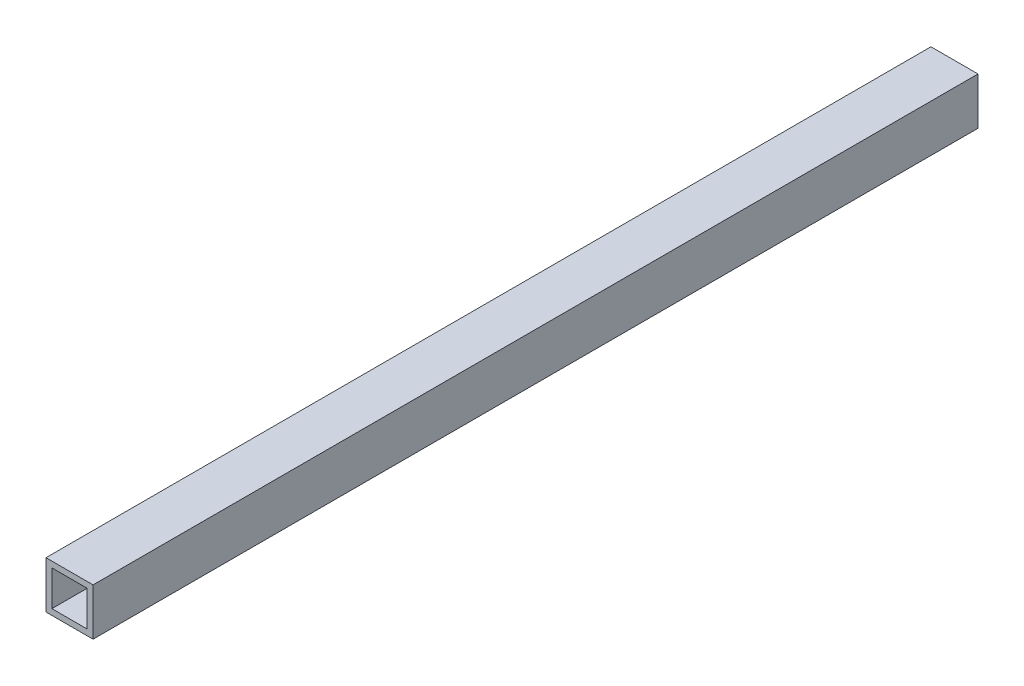
SolidWorks part; units mm, degrees
material "6061 Alloy"
ref_plane "Front Plane" through (0, 0, 0) normal (0, 0, 1) x (1, 0, 0)
ref_plane "Top Plane" through (0, 0, 0) normal (0, 1, 0) x (1, 0, 0)
ref_plane "Right Plane" through (0, 0, 0) normal (1, 0, 0) x (0, 0, -1)
sketch "Sketch1" plane through (0, 0, 0) normal (0, 0, 1) x (1, 0, 0)
  line L0 (12.7, 0) -> (9.525, 0) construction
  line L1 (-12.7, 0) -> (12.7, 0) construction
  line L2 (0, 12.7) -> (0, -12.7)
  point P7 (0, 0)
sketch "Sketch2" plane through (0, 0, 0) normal (1, 0, 0) x (0, 0, -1)
  line L0 (238.76, 0) -> (-238.76, 0)
  point P4 (0, 0)
  dimension "Length" = 477.52
sketch "Sketch3" plane through (0, 0, 0) normal (0, 0, 1) x (1, 0, 0)
  line L0 (-12.7, 0) -> (12.7, 0) construction
  line L5 (12.7, -12.7) -> (-12.7, -12.7)
  line L6 (12.7, -12.7) -> (12.7, 12.7)
  line L11 (12.7, 12.7) -> (-12.7, 12.7)
  line L12 (-12.7, -12.7) -> (-12.7, 12.7)
  line L14 (12.7, -12.7) -> (-12.7, 12.7) construction
  line L15 (12.7, 12.7) -> (-12.7, -12.7) construction
  line L16 (9.525, -9.525) -> (-9.525, -9.525)
  line L17 (9.525, -9.525) -> (9.525, 9.525)
  line L18 (9.525, 9.525) -> (-9.525, 9.525)
  line L19 (-9.525, -9.525) -> (-9.525, 9.525)
  line L20 (9.525, -9.525) -> (-9.525, 9.525) construction
  line L21 (9.525, 9.525) -> (-9.525, -9.525) construction
  point P0 (0, 0)
  point P5 (0, 0)
  point P13 (9.525, -12.7)
  dimension "D1" = 3.175
extrude "Boss-Extrude1" add sketch "Sketch3" along normal up to vertex (238.76 mm away) and the other way up to vertex (238.76 mm away) up to point (0, 0, 238.76) other way up to point (0, 0, -238.76)
sketch "Sketch5" plane through (0, 0, 0) normal (1, 0, 0) x (0, 0, -1)
  line L0 (-238.76, 0) -> (238.76, 0) construction
  line L3 (-238.76, -12.7) -> (-238.76, 12.7) construction
  line L4 (238.76, -12.7) -> (238.76, 12.7) construction
  point P6 (-210.185, 0)
  point P7 (-200.66, 0)
  point P8 (200.66, 0)
  point P10 (210.185, 0)
  dimension "D1" = 28.575
  dimension "D2" = 38.1
  dimension "D3" = 28.575
  dimension "D4" = 38.1
equation "\"D1@Sketch3\"=\"Wall thickness@Sketch1\""
equation "\"D1@Sketch5\"=\"Width@Sketch1\"*1.125"
equation "\"D2@Sketch5\"=\"Width@Sketch1\"*1.5"
equation "\"D3@Sketch5\"=\"D1@Sketch5\""
equation "\"D4@Sketch5\"=\"D2@Sketch5\""
equation "\"D2@Sketch3\"=\"Wall Thickness@Sketch1\""
